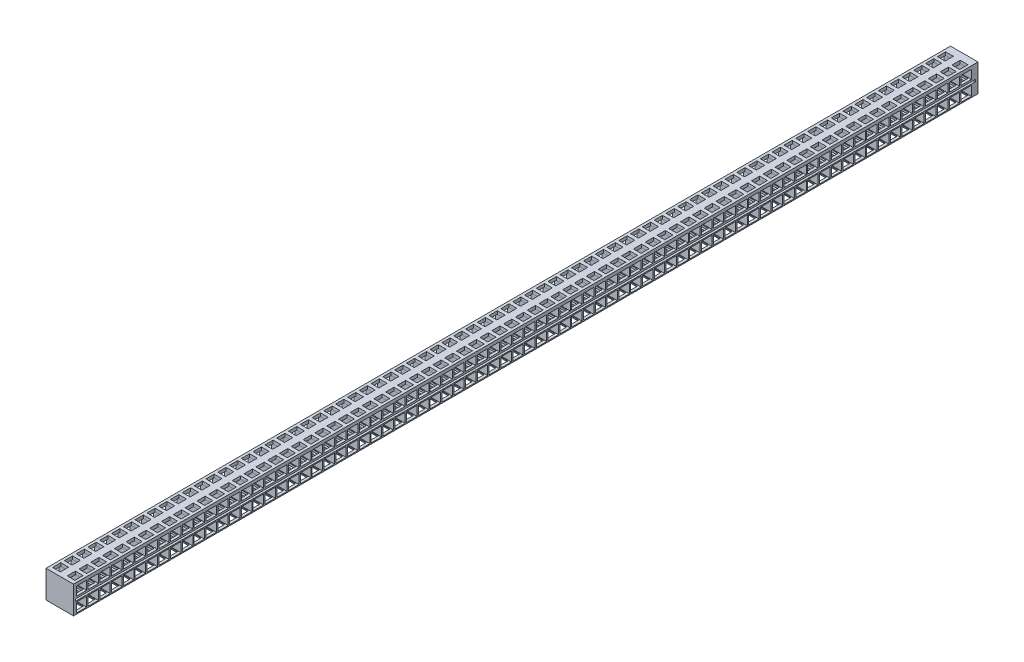
SolidWorks part; units mm, degrees
ref_plane "Alzado" through (0, 0, 0) normal (0, 0, 1) x (1, 0, 0)
ref_plane "Planta" through (0, 0, 0) normal (0, 1, 0) x (1, 0, 0)
ref_plane "Vista lateral" through (0, 0, 0) normal (1, 0, 0) x (0, 0, -1)
sketch "Croquis1" plane through (0, 0, 0) normal (0, 0, 1) x (1, 0, 0)
  line L1 (-175, 175) -> (175, 175)
  line L2 (-175, 175) -> (-175, -175)
  line L3 (-175, -175) -> (175, -175)
  line L4 (175, 175) -> (175, -175)
  line L5 (-175, 175) -> (175, -175) construction
  line L6 (-175, -175) -> (175, 175) construction
  point P0 (0, 0)
  dimension "D1" = 350
  dimension "D2" = 350
extrude "Saliente-Extruir1" add sketch "Croquis1" along normal blind 11500
sketch "Croquis2" plane through (175, 0, 0) normal (1, 0, 0) x (0, 0, -1)
  line L0 (-11500, 0) -> (0, 0)
  line L1 (-11500, -175) -> (-11500, 175) construction
  line L2 (0, 0) -> (0, -26.0444)
  line L3 (0, -175) -> (0, 175) construction
  line L4 (0, -26.0444) -> (-11500, -26.0444)
  line L5 (-11500, -26.0444) -> (-11475.2232, -26.0444)
  line L6 (-11475.2232, -26.0444) -> (-11475.2232, 0)
  line L7 (-33.7577, 0) -> (-33.7577, -26.0444)
extrude "Cortar-Extruir1" cut sketch "Croquis2" against normal blind 11500 contours L7 L0 L6 L4 region at (175, -13.0222, 5754.4904)
sketch "Croquis3" plane through (175, 0, 0) normal (1, 0, 0) x (0, 0, -1)
  line L1 (-11465.3656, 134.979) -> (-11333.4634, 134.979)
  line L2 (-11465.3656, 134.979) -> (-11465.3656, 23.9035)
  line L3 (-11465.3656, 23.9035) -> (-11333.4634, 23.9035)
  line L4 (-11333.4634, 134.979) -> (-11333.4634, 23.9035)
  line L5 (-11465.3656, 134.979) -> (-11333.4634, 23.9035) construction
  line L6 (-11465.3656, 23.9035) -> (-11333.4634, 134.979) construction
  line L7 (-11465.3656, -40.312) -> (-11333.4634, -40.312)
  line L8 (-11465.3656, -40.312) -> (-11465.3656, -161.8009)
  line L9 (-11465.3656, -161.8009) -> (-11333.4634, -161.8009)
  line L10 (-11333.4634, -40.312) -> (-11333.4634, -161.8009)
  line L11 (-11465.3656, -40.312) -> (-11333.4634, -161.8009) construction
  line L12 (-11465.3656, -161.8009) -> (-11333.4634, -40.312) construction
  point P0 (-11399.4145, 79.4412)
  point P5 (-11399.4145, -101.0565)
extrude "Cortar-Extruir2" cut sketch "Croquis3" against normal blind 11500
pattern_linear "MatrizL1" count 76 spacing 150 along (0, 0, -1) of "Cortar-Extruir2"
sketch "Croquis4" plane through (0, 175, 0) normal (0, 1, 0) x (1, 0, 0)
  line L1 (-141.9416, -11449.4866) -> (-43.9533, -11449.4866)
  line L2 (-141.9416, -11449.4866) -> (-141.9416, -11344.4991)
  line L3 (-141.9416, -11344.4991) -> (-43.9533, -11344.4991)
  line L4 (-43.9533, -11449.4866) -> (-43.9533, -11344.4991)
  line L5 (-141.9416, -11449.4866) -> (-43.9533, -11344.4991) construction
  line L6 (-141.9416, -11344.4991) -> (-43.9533, -11449.4866) construction
  line L7 (43.5363, -11449.4866) -> (141.5246, -11449.4866)
  line L8 (43.5363, -11449.4866) -> (43.5363, -11344.4991)
  line L9 (43.5363, -11344.4991) -> (141.5246, -11344.4991)
  line L10 (141.5246, -11449.4866) -> (141.5246, -11344.4991)
  line L11 (43.5363, -11449.4866) -> (141.5246, -11344.4991) construction
  line L12 (43.5363, -11344.4991) -> (141.5246, -11449.4866) construction
  point P0 (-92.9474, -11396.9928)
  point P5 (92.5305, -11396.9928)
extrude "Cortar-Extruir3" cut sketch "Croquis4" against normal blind 11500
pattern_linear "MatrizL2" count 76 spacing 150 along (0, 0, -1) of "Cortar-Extruir3"
